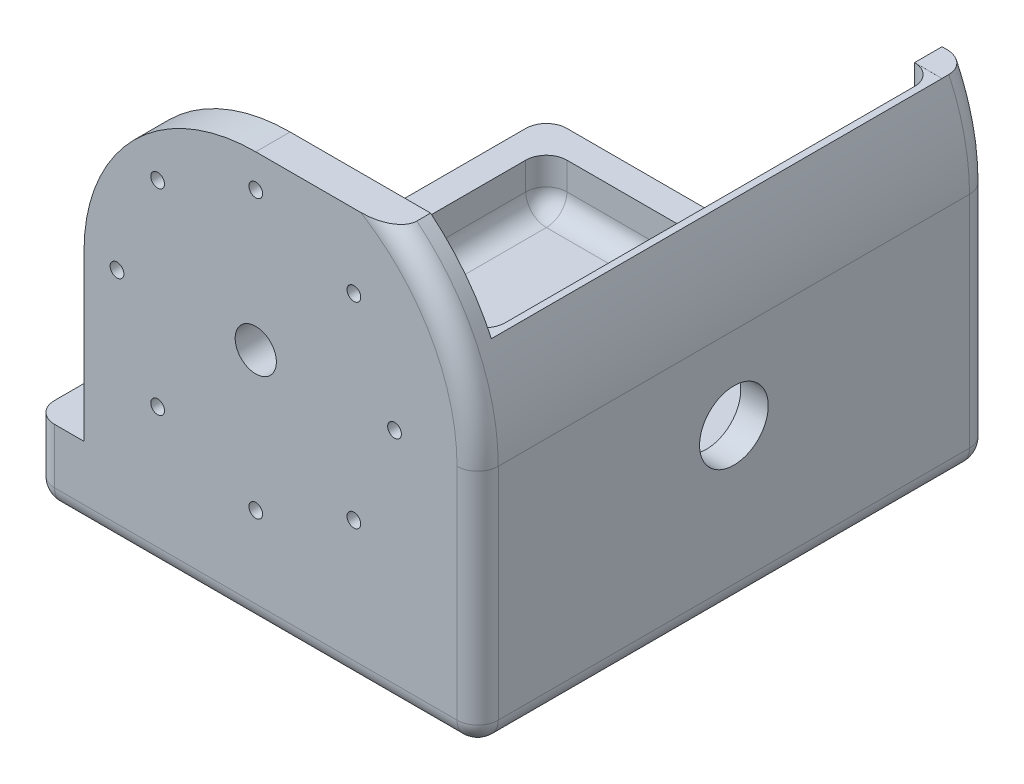
SolidWorks part; units mm, degrees
ref_plane "前视基准面" through (0, 0, 0) normal (0, 0, 1) x (1, 0, 0)
ref_plane "上视基准面" through (0, 0, 0) normal (0, 1, 0) x (1, 0, 0)
ref_plane "右视基准面" through (0, 0, 0) normal (1, 0, 0) x (0, 0, -1)
sketch "草图1" plane through (0, 0, 0) normal (0, 1, 0) x (1, 0, 0)
  line L1 (-32.3, 37.3) -> (32.3, 37.3)
  line L2 (-32.3, 37.3) -> (-32.3, -37.3)
  line L3 (-32.3, -37.3) -> (32.3, -37.3)
  line L4 (32.3, 37.3) -> (32.3, -37.3)
  line L5 (-32.3, 37.3) -> (32.3, -37.3) construction
  line L6 (-32.3, -37.3) -> (32.3, 37.3) construction
  point P0 (0, 0)
  dimension "D1" = 74.6
  dimension "D2" = 64.6
extrude "凸台-拉伸1" add sketch "草图1" along normal blind 4
sketch "草图2" plane through (0, 0, 37.3) normal (0, 0, 1) x (1, 0, 0)
  line L0 (-32.3, 0) -> (-32.3, 11)
  line L1 (-25, 35) -> (-25, 11)
  line L2 (-25, 11) -> (-32.3, 11)
  line L3 (32.3, 35) -> (32.3, 0)
  line L4 (-32.3, 0) -> (32.3, 0) construction
  line L5 (-32.3, 0) -> (32.3, 0)
  line L6 (0, 60) -> (20.4521, 60)
  arc A0 (32.3, 35) -> (20.4521, 60) centre (0, 35) ccw
  arc A1 (-25, 35) -> (0, 60) centre (0, 35) cw
  dimension "D1" = 24
  dimension "D2" = 25
  dimension "D3" = 20.4521
  dimension "D4" = 35
  dimension "D5" = 64.6
extrude "凸台-拉伸2" add sketch "草图2" against normal blind 5
sketch "草图3" plane through (0, 0, -37.3) normal (0, 0, -1) x (-1, 0, 0)
  line L0 (-32.3, 0) -> (-32.3, 35)
  line L1 (-32.3, 0) -> (32.3, 0)
  line L2 (32.3, 0) -> (32.3, 11)
  line L3 (25, 11) -> (32.3, 11) construction
  line L4 (-25.3, 48.6) -> (-29.2973, 48.6)
  line L5 (32.3, 11) -> (32.3, 4) construction
  line L6 (-25.3, 26) -> (-25.3, 48.6)
  line L7 (-10.3, 11) -> (32.3, 11)
  arc A0 (-32.3, 35) -> (-29.2973, 48.6) centre (0, 35) cw
  arc A3 (-25.3, 26) -> (-10.3, 11) centre (-10.3, 26) ccw
  arc A6 (-20.4521, 60) -> (-32.3, 35) centre (0, 35) ccw construction
  dimension "D2" = 15
  dimension "D3" = 48.6
  dimension "D1" = 7
extrude "凸台-拉伸3" add sketch "草图3" against normal blind 4
sketch "草图4" plane through (0, 0, 32.3) normal (0, 0, -1) x (-1, 0, 0)
  line L0 (-32.3, 4) -> (-28.3, 4)
  line L1 (-32.3, 4) -> (32.3, 4) construction
  line L2 (-32.3, 4) -> (-32.3, 35)
  line L3 (-28.3, 4) -> (-28.3, 48.5941)
  line L5 (-28.3, 48.5941) -> (-29.3, 48.5941)
  arc A0 (-32.3, 35) -> (-29.3, 48.5941) centre (0, 35) cw
  arc A1 (-20.4521, 60) -> (-32.3, 35) centre (0, 35) ccw construction
  dimension "D1" = 4
  dimension "D2" = 1
extrude "凸台-拉伸4" add sketch "草图4" along normal up to next
sketch "草图9" plane through (0, 0, 32.3) normal (0, 0, -1) x (-1, 0, 0)
  line L1 (32.3, 11) -> (32.3, 4)
  line L2 (32.3, 4) -> (28.3, 4)
  line L3 (32.3, 4) -> (-28.3, 4) construction
  line L4 (28.3, 4) -> (28.3, 11)
  line L5 (25, 11) -> (32.3, 11) construction
  line L6 (28.3, 11) -> (32.3, 11)
  dimension "D1" = 4
extrude "凸台-拉伸8" add sketch "草图9" along normal up to next
sketch "草图10" plane through (0, 0, 0) normal (0, -1, 0) x (1, 0, 0)
  circle A0 centre (0, 0) radius 4
  circle A1 centre (6.8, 0) radius 0.75
  circle A2 centre (0, -6.8) radius 0.75
  circle A3 centre (-6.8, 0) radius 0.75
  circle A4 centre (0, 6.8) radius 0.75
  point P14 (0, 0)
  dimension "D1" = 8
  dimension "D2" = 1.5
  dimension "D3" = 6.8
  dimension "D4" = 4
sketch "草图11" plane through (0, 0, 32.3) normal (0, 0, -1) x (-1, 0, 0)
  circle A0 centre (20.2, 35) radius 1
  circle A1 centre (14.2836, 20.7164) radius 1
  circle A2 centre (0, 14.8) radius 1
  circle A3 centre (-14.2836, 20.7164) radius 1
  circle A4 centre (-20.2, 35) radius 1
  circle A5 centre (-14.2836, 49.2836) radius 1
  circle A6 centre (0, 55.2) radius 1
  circle A7 centre (14.2836, 49.2836) radius 1
  circle A8 centre (0, 35) radius 3
  point P2 (0, 35)
  point P20 (0, 35)
  dimension "D2" = 2
  dimension "D5" = 6
  dimension "D1" = 20.2
  dimension "D3" = 35
  dimension "D4" = 8
extrude "切除-拉伸1" cut sketch "草图11" against normal through all
fillet "圆角2" radius 3 18 edges at (28.3, 4, -0.5) (32.3, 0, 0) (29.1881, 48.8327, 37.3) (31.5404, 41.9638, -37.3) (32.3, 17.5, 37.3) (32.3, 17.5, -37.3) (0, 4, 32.3) (28.3, 26.2971, 32.3) (0, 4, -33.3) (28.3, 26.2971, -33.3) (-32.3, 0, 0) (0, 0, 37.3) (0, 0, -37.3) (-28.3, 4, -0.5) (-32.3, 5.5, -37.3) (-28.3, 7.5, -33.3) (-32.3, 5.5, 37.3) (-28.3, 7.5, 32.3)
sketch "草图12" plane through (28.3, 0, 0) normal (-1, 0, 0) x (0, 0, 1)
  line L0 (-34.3, 3) -> (34.3, 3) construction
  circle A0 centre (0, 23) radius 5
  dimension "D1" = 10
  dimension "D2" = 20
extrude "切除-拉伸2" cut sketch "草图12" against normal blind 10
sketch "草图13" plane through (-32.3, 0, 0) normal (-1, 0, 0) x (0, 0, 1)
  line L0 (-34.3, 11) -> (34.3, 11) construction
  line L1 (-30.3, 11) -> (29.3, 11) construction
  line L2 (-6.3443, 11) -> (6.3443, 11)
  arc A0 (-6.3443, 11) -> (6.3443, 11) centre (0, 13.958) ccw
  point P5 (-0.5, 11)
  dimension "D1" = 7
  dimension "D2" = 3
extrude "切除-拉伸3" cut sketch "草图13" against normal blind 10
ref_plane "基准面1" through (-15, 0, 0) normal (-1, 0, 0) x (0, 0, 1)
sketch "草图14" plane through (-15, 0, 0) normal (-1, 0, 0) x (0, 0, 1)
  line L0 (22.3, 4) -> (32.3, 17)
  line L2 (-30.3, 4) -> (29.3, 4) construction
  line L3 (32.3, 17) -> (32.3, 4)
  line L5 (32.3, 4) -> (22.3, 4)
  line L6 (32.3, 35) -> (32.3, 11) construction
  dimension "D1" = 10
  dimension "D2" = 13
extrude "凸台-拉伸9" add sketch "草图14" along normal blind 5
ref_plane "基准面2" through (15, 0, 0) normal (1, 0, 0) x (0, 0, -1)
sketch "草图15" plane through (15, 0, 0) normal (1, 0, 0) x (0, 0, -1)
  line L0 (-22.3, 4) -> (-32.3, 4)
  line L2 (-32.3, 4) -> (-32.3, 17)
  line L4 (-32.3, 17) -> (-22.3, 4)
  line L5 (30.3, 4) -> (-29.3, 4) construction
  line L6 (-32.3, 35) -> (-32.3, 11) construction
  dimension "D1" = 13
  dimension "D2" = 10
extrude "凸台-拉伸10" add sketch "草图15" along normal blind 4
extrude "切除-拉伸4" cut sketch "草图10" against normal blind 5
sketch "草图17" plane through (0, 0, 0) normal (0, -1, 0) x (1, 0, 0)
  circle A0 centre (0, 0) radius 10
  dimension "D1" = 20
extrude "切除-拉伸5" cut sketch "草图17" against normal blind 1.5
